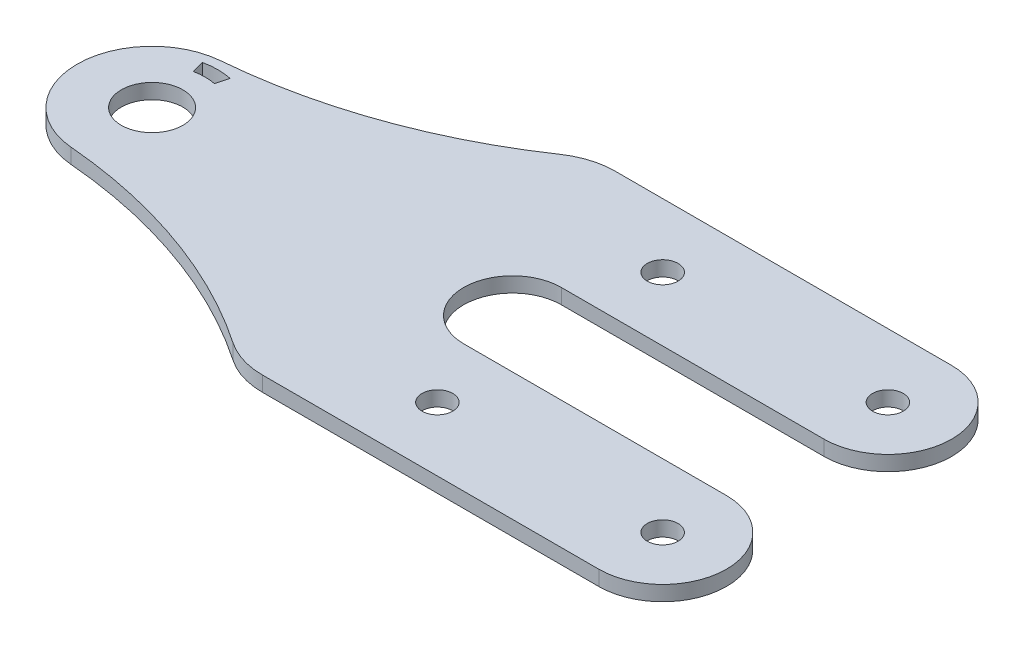
SolidWorks part; units mm, degrees
ref_plane "Front Plane" through (0, 0, 0) normal (0, 0, 1) x (1, 0, 0)
ref_plane "Top Plane" through (0, 0, 0) normal (0, 1, 0) x (1, 0, 0)
ref_plane "Right Plane" through (0, 0, 0) normal (1, 0, 0) x (0, 0, -1)
sketch "Sketch1" plane through (0, 0, 0) normal (0, 1, 0) x (1, 0, 0)
  line L0 (35, -10) -> (35, -23.5)
  line L1 (0, 10) -> (35, 10)
  line L3 (0, -10) -> (35, -10)
  line L5 (35, 23.5) -> (83, 23.5)
  line L6 (35, 23.5) -> (35, 10)
  line L7 (35, -23.5) -> (83, -23.5)
  line L9 (83, 6.5) -> (48, 6.5)
  line L11 (83, -6.5) -> (48, -6.5)
  line L15 (53, 15) -> (83, 15) construction
  line L16 (53, 15) -> (53, -15) construction
  line L17 (53, -15) -> (83, -15) construction
  line L18 (83, 15) -> (83, -15) construction
  arc A0 (0, 10) -> (0, -10) centre (0, 0) ccw
  circle A1 centre (0, 0) radius 4.1
  arc A2 (83, 6.5) -> (83, 23.5) centre (83, 15) ccw
  arc A3 (83, -23.5) -> (83, -6.5) centre (83, -15) ccw
  circle A4 centre (53, 15) radius 2.05
  circle A5 centre (83, 15) radius 2.05
  circle A6 centre (53, -15) radius 2.05
  circle A7 centre (83, -15) radius 2.05
  arc A8 (48, 6.5) -> (48, -6.5) centre (48, 0) ccw
  point P16 (0, 0)
  point P22 (44.4626, 1.749)
  point P23 (0, 0)
  dimension "D1" = 8.2
  dimension "D2" = 20
  dimension "D3" = 35
  dimension "D6" = 83
  dimension "D9" = 4.1
  dimension "D4" = 17
  dimension "D5" = 13
  dimension "D7" = 17
  dimension "D8" = 30
  dimension "D10" = 35
extrude "Boss-Extrude1" add sketch "Sketch1" along normal blind 2
sketch "Sketch2" plane through (0, 2, 0) normal (0, 1, 0) x (1, 0, 0)
  line L0 (-1.8407, 8.5542) -> (-1.4, 6.9096)
  line L1 (1.8407, 8.5542) -> (1.4, 6.9096)
  line L2 (0, 8.75) -> (0, 7.05) construction
  arc A0 (1.8407, 8.5542) -> (-1.8407, 8.5542) centre (0, 0) ccw
  arc A1 (1.4, 6.9096) -> (-1.4, 6.9096) centre (0, 0) ccw
  dimension "D1" = 14.1
  dimension "D2" = 17.5
  dimension "D3" = 15
  dimension "D4" = 15
  dimension "D5" = 1.4
  dimension "D6" = 1.4
extrude "Cut-Extrude1" cut sketch "Sketch2" against normal through all
fillet "Fillet1" radius 70 2 edges at (35, 1, -10) (35, 1, 10)
fillet "Fillet2" radius 10 2 edges at (35, 1, 23.5) (35, 1, -23.5)
